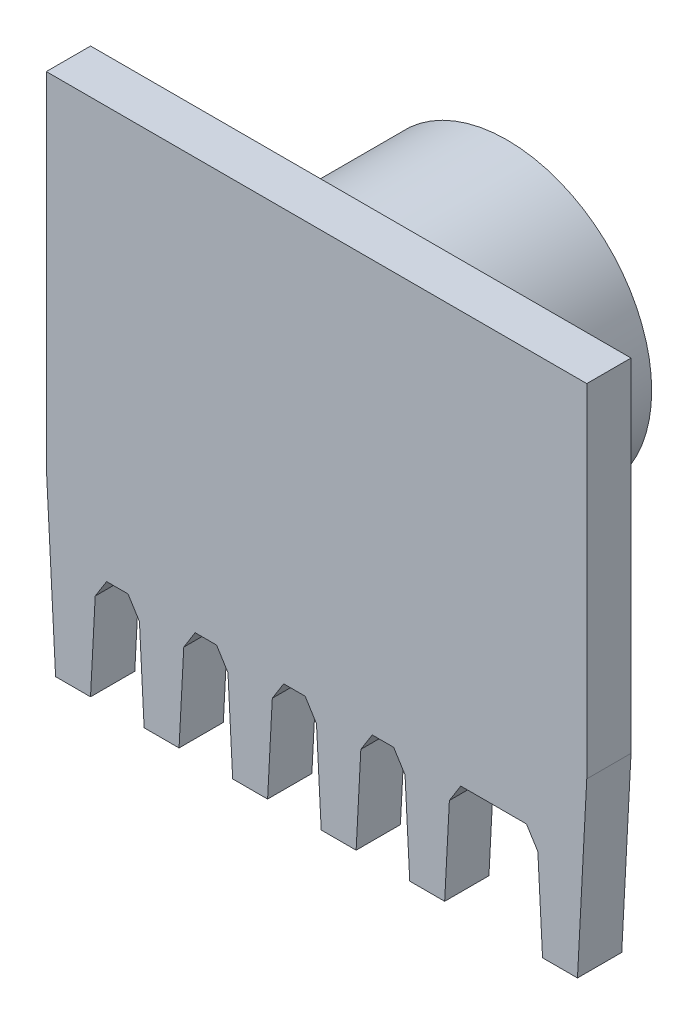
SolidWorks part; units mm, degrees
ref_plane "Front Plane" through (0, 0, 0) normal (0, 0, 1) x (1, 0, 0)
ref_plane "Top Plane" through (0, 0, 0) normal (0, 1, 0) x (1, 0, 0)
ref_plane "Right Plane" through (0, 0, 0) normal (1, 0, 0) x (0, 0, -1)
sketch "Sketch1" plane through (0, 0, 0) normal (0, 0, 1) x (1, 0, 0)
  line L0 (0, 0) -> (0, 17.6) construction
  line L1 (0, 17.6) -> (18.3124, 17.6) construction
  line L2 (18.3124, 17.6) -> (18.3124, 0) construction
  line L3 (18.3124, 0) -> (0, 0) construction
  line L4 (0, 3) -> (18.3124, 3) construction
  line L5 (0, 6) -> (18.3124, 6) construction
  line L6 (0.9062, 6) -> (0.9062, 0) construction
  line L7 (3.9062, 6) -> (3.9062, 0) construction
  line L8 (6.9062, 6) -> (6.9062, 0) construction
  line L9 (9.9062, 6) -> (9.9062, 0) construction
  line L10 (12.9062, 6) -> (12.9062, 0) construction
  line L11 (17.4062, 6) -> (17.4062, 0) construction
  line L12 (0.9062, 3) -> (3.9062, 3) construction
  line L13 (3.9062, 3) -> (6.9062, 3) construction
  line L14 (6.9062, 3) -> (9.9062, 3) construction
  line L15 (9.9062, 3) -> (12.9062, 3) construction
  line L16 (12.9062, 3) -> (17.4062, 3) construction
  line L17 (0.9062, 3) -> (0, 3) construction
  line L18 (17.4062, 3) -> (18.3124, 3) construction
  line L19 (2.4062, 3) -> (2.4062, 0) construction
  line L20 (5.4062, 3) -> (5.4062, 0) construction
  line L21 (8.4062, 3) -> (8.4062, 0) construction
  line L22 (11.4062, 3) -> (11.4062, 0) construction
  line L23 (15.1562, 3) -> (15.1562, 0) construction
  line L24 (14.4062, 3.75) -> (15.9062, 3.75) construction
  line L25 (0, 6) -> (0.3144, 0)
  line L26 (0.3144, 0) -> (1.4979, 0)
  line L27 (1.4979, 0) -> (1.6572, 3.0393)
  line L28 (3.1552, 3.0393) -> (3.3144, 0)
  line L29 (3.3144, 0) -> (4.4979, 0)
  line L30 (4.4979, 0) -> (4.6572, 3.0393)
  line L31 (6.1552, 3.0393) -> (6.3144, 0)
  line L32 (6.3144, 0) -> (7.4979, 0)
  line L33 (7.4979, 0) -> (7.6572, 3.0393)
  line L34 (9.1552, 3.0393) -> (9.3144, 0)
  line L35 (9.3144, 0) -> (10.4979, 0)
  line L36 (10.4979, 0) -> (10.6572, 3.0393)
  line L37 (12.1552, 3.0393) -> (12.3144, 0)
  line L38 (12.3144, 0) -> (13.4979, 0)
  line L39 (13.4979, 0) -> (13.6572, 3.0393)
  line L40 (16.6552, 3.0393) -> (16.8144, 0)
  line L41 (16.8144, 0) -> (17.9979, 0)
  line L42 (17.9979, 0) -> (18.3124, 6)
  line L44 (1.6572, 3.0393) -> (2.0426, 3.656)
  line L45 (0, 6) -> (0, 17.6)
  line L46 (0, 17.6) -> (18.3124, 17.6)
  line L47 (18.3124, 17.6) -> (18.3124, 6)
  line L48 (9.1562, 17.6) -> (9.1562, 6) construction
  line L49 (2.0426, 3.656) -> (2.7698, 3.656)
  line L50 (2.7698, 3.656) -> (3.1552, 3.0393)
  line L51 (4.6572, 3.0393) -> (5.0426, 3.656)
  line L52 (5.0426, 3.656) -> (5.7698, 3.656)
  line L53 (5.7698, 3.656) -> (6.1552, 3.0393)
  line L54 (7.6572, 3.0393) -> (8.0426, 3.656)
  line L55 (8.0426, 3.656) -> (8.7698, 3.656)
  line L56 (8.7698, 3.656) -> (9.1552, 3.0393)
  line L57 (10.6572, 3.0393) -> (11.0426, 3.656)
  line L58 (11.0426, 3.656) -> (11.7698, 3.656)
  line L59 (11.7698, 3.656) -> (12.1552, 3.0393)
  line L60 (13.6572, 3.0393) -> (14.0426, 3.656)
  line L61 (14.0426, 3.656) -> (16.2698, 3.656)
  line L62 (16.2698, 3.656) -> (16.6552, 3.0393)
  line L63 (18.3124, 17.6) -> (18.3124, 18.1) construction
  line L64 (18.3124, 18.1) -> (0, 18.1) construction
  line L65 (0, 18.1) -> (0, 17.6) construction
  arc A0 (3.1552, 3.0393) -> (1.6572, 3.0393) centre (2.4062, 3) ccw construction
  arc A1 (6.1552, 3.0393) -> (4.6572, 3.0393) centre (5.4062, 3) ccw construction
  arc A2 (9.1552, 3.0393) -> (7.6572, 3.0393) centre (8.4062, 3) ccw construction
  arc A3 (12.1552, 3.0393) -> (10.6572, 3.0393) centre (11.4062, 3) ccw construction
  arc A4 (13.6572, 3.0393) -> (14.4062, 3.75) centre (14.4062, 3) cw construction
  arc A5 (16.6552, 3.0393) -> (15.9062, 3.75) centre (15.9062, 3) ccw construction
  dimension "D7" = 0.75
  dimension "D1" = 3
  dimension "D2" = 6
  dimension "D3" = 11.6
  dimension "D4" = 3
  dimension "D5" = 0.5
  dimension "D6" = 4.5
  dimension "D8" = 3
  dimension "D9" = 18.3124
  dimension "D10" = 17.6
extrude "Boss-Extrude1" add sketch "Sketch1" along normal blind 1.5
sketch "Sketch3" plane through (0, 0, 0) normal (0, 0, 1) x (1, 0, 0)
  line L0 (-0.4005, 6) -> (18.7129, 6)
  line L1 (18.7129, 3) -> (-0.4005, 3) construction
  line L2 (-0.4005, 0) -> (18.7129, 0) construction
  line L3 (-0.4005, -0.5) -> (18.7129, -0.5) construction
  line L4 (18.7129, -0.5) -> (18.7129, 6) construction
  line L5 (-0.4005, 6) -> (-0.4005, -0.5) construction
  line L6 (18.3124, 0) -> (0, 0) construction
  line L7 (0, 3) -> (18.3124, 3) construction
  line L8 (0, 6) -> (18.3124, 6) construction
  line L9 (0.3407, -0.5) -> (0, 6) construction
  line L10 (18.3124, 6) -> (17.9717, -0.5) construction
  line L11 (17.9979, 0) -> (18.3124, 6) construction
  line L12 (0, 6) -> (0.3144, 0) construction
  line L13 (5.4062, 6) -> (5.4062, -0.5) construction
  line L14 (3.9062, 6) -> (3.9062, -0.5) construction
  line L15 (5.4062, 3) -> (5.4062, 0) construction
  line L16 (3.1572, 3) -> (3.3407, -0.5) construction
  line L17 (2.7567, 3) -> (2.9401, -0.5)
  line L18 (3.1552, 3.0393) -> (3.3144, 0) construction
  line L19 (2.9401, -0.5) -> (4.8723, -0.5)
  line L20 (4.8723, -0.5) -> (5.0557, 3)
  line L21 (2.8484, 1.25) -> (3.2478, 1.2709) construction
  line L22 (5.9401, -0.5) -> (5.7567, 3)
  line L26 (7.8723, -0.5) -> (5.9401, -0.5)
  line L27 (8.0557, 3) -> (7.8723, -0.5)
  line L30 (2.4062, -0.5) -> (2.4062, 6) construction
  line L31 (2.4062, 3) -> (2.4062, 0) construction
  line L32 (8.4062, 6) -> (8.4062, -0.5) construction
  line L34 (11.4062, -0.5) -> (11.4062, 6) construction
  line L35 (15.1562, -0.5) -> (15.1562, 6) construction
  line L36 (8.4062, 3) -> (8.4062, 0) construction
  line L37 (11.4062, 3) -> (11.4062, 0) construction
  line L38 (15.1562, 3) -> (15.1562, 0) construction
  line L39 (10.8723, -0.5) -> (11.0557, 3)
  line L40 (8.9401, -0.5) -> (10.8723, -0.5)
  line L41 (8.7567, 3) -> (8.9401, -0.5)
  line L42 (11.9401, -0.5) -> (11.7567, 3)
  line L43 (13.8723, -0.5) -> (11.9401, -0.5)
  line L44 (14.0557, 3) -> (13.8723, -0.5)
  line L45 (16.4401, -0.5) -> (18.3723, -0.5)
  line L46 (16.2567, 3) -> (16.4401, -0.5)
  line L47 (18.3723, -0.5) -> (18.7129, 6)
  line L48 (1.8723, -0.5) -> (-0.0599, -0.5)
  line L49 (2.0557, 3) -> (1.8723, -0.5)
  line L50 (-0.0599, -0.5) -> (-0.4005, 6)
  line L51 (16.2567, 3) -> (14.0557, 3)
  line L52 (11.7567, 3) -> (11.0557, 3)
  line L53 (8.7567, 3) -> (8.0557, 3)
  line L54 (5.7567, 3) -> (5.0557, 3)
  line L55 (2.7567, 3) -> (2.0557, 3)
  dimension "D1" = 0.5
  dimension "D2" = 0.4
ref_plane "Plane1" through (3.9062, 0, 0) normal (1, 0, 0) x (0, 0, -1)
sketch "Sketch4" plane through (3.9062, 0, 0) normal (1, 0, 0) x (0, 0, -1)
  line L0 (0, 6) -> (0, -0.5) construction
  line L1 (0.6, 6) -> (-2.1, 6) construction
  line L2 (0.6, 6) -> (0.6, -0.5) construction
  line L3 (0.6, -0.5) -> (-2.1, -0.5) construction
  line L4 (-2.1, 6) -> (-2.1, -0.5) construction
  line L5 (-0.75, -0.5) -> (-0.75, 6) construction
  line L6 (-1.5, 6) -> (-1.5, -0.5) construction
  line L7 (0.6, 2.4005) -> (-2.1, 2.4005) construction
  line L8 (0.3, 6) -> (0.3, -0.5) construction
  line L9 (0.6, 2.4005) -> (3.846, 6) construction
  line L10 (2.2302, 6) -> (0.6, 4.1923) construction
  line L11 (0.6, 4.1923) -> (1.7139, 3.1878) construction
  line L12 (1.7139, 3.1878) -> (4.25, 6)
  line L13 (4.25, 6) -> (0.6, 6) construction
  line L14 (0.3, 1) -> (-1.8, 1) construction
  line L15 (-2.1, 0) -> (0.6, 0) construction
  line L16 (1.7139, 3.1878) -> (1.4912, 3.3887)
  line L17 (1.4912, 3.3887) -> (0.6, 2.4005)
  line L18 (-3.2139, 3.1878) -> (-5.75, 6)
  line L19 (-3.2139, 3.1878) -> (-2.9912, 3.3887)
  line L20 (-2.9912, 3.3887) -> (-2.1, 2.4005)
  line L21 (-2.1, 6) -> (-5.75, 6) construction
  line L22 (0.6, 3.0724) -> (3.2401, 6) construction
  arc A0 (0.4965, 2.2224) -> (0.6, -0.5) centre (4.2, 1) ccw
  arc A1 (0.6, 2.4005) -> (0.4965, 2.2224) centre (0.9713, 2.0656) ccw
  arc A2 (-2.1, 2.4005) -> (-1.9965, 2.2224) centre (-2.4713, 2.0656) cw
  arc A3 (-1.9965, 2.2224) -> (-2.1, -0.5) centre (-5.7, 1) cw
  dimension "D6" = 0.5
  dimension "D1" = 0.6
  dimension "D2" = 0.3
  dimension "D3" = 1.5
  dimension "D4" = 1
  dimension "D5" = 0.3
  dimension "D7" = 10
sketch "Sketch5" plane through (0, 0, 0) normal (1, 0, 0) x (0, 0, -1)
  line L0 (2.2302, 6) -> (0.6, 4.1923) construction
  line L1 (0.6, 4.1923) -> (1.7139, 3.1878) construction
  line L2 (1.7139, 3.1878) -> (4.25, 6) construction
  line L3 (2.2302, 6) -> (0.6, 4.1923) construction
  line L4 (0.6, 4.1923) -> (1.7139, 3.1878) construction
  line L5 (1.7139, 3.1878) -> (4.25, 6) construction
ref_plane "Plane2" through (0, 2.6105, -2.3541) normal (0, 0.7426, -0.6697) x (1, 0, 0)
sketch "Sketch6" plane through (0, 2.6105, -2.3541) normal (0, 0.7426, -0.6697) x (1, 0, 0)
  line L1 (3.9062, -2.362) -> (3.9062, -0.862) construction
  line L2 (3.9062, -2.362) -> (3.9062, -5.0612) construction
  line L3 (4.6562, -5.0612) -> (3.1562, -5.0612)
  line L4 (4.6562, -1.612) -> (3.1562, -1.612) construction
  line L5 (3.1562, -1.612) -> (3.1562, -5.0612)
  line L6 (4.6562, -1.612) -> (4.6562, -5.0612)
  line L10 (2.4062, -5.0612) -> (15.1562, -5.0612) construction
  line L11 (15.1562, -5.0612) -> (15.1562, -0.862) construction
  line L12 (15.1562, -0.862) -> (2.4062, -0.862) construction
  line L13 (2.4062, -0.862) -> (2.4062, -5.0612) construction
  line L14 (15.1562, 0.3349) -> (15.1562, -4.0182) construction
  line L15 (2.4062, 0.3349) -> (2.4062, -4.0182) construction
  line L16 (11.4062, -5.0612) -> (11.4062, -0.862) construction
  line L17 (8.4062, -5.0612) -> (8.4062, -0.862) construction
  line L18 (5.4062, -5.0612) -> (5.4062, -0.862) construction
  line L19 (5.4062, -4.0182) -> (5.4062, 0.3349) construction
  line L20 (8.4062, -4.0182) -> (8.4062, 0.3349) construction
  line L21 (11.4062, 0.3349) -> (11.4062, -4.0182) construction
  line L22 (0.1562, -1.612) -> (0.1562, -5.0612)
  line L23 (0.1562, -5.0612) -> (1.6562, -5.0612)
  line L24 (1.6562, -1.612) -> (1.6562, -5.0612)
  line L25 (7.6562, -1.612) -> (7.6562, -5.0612)
  line L26 (6.1562, -5.0612) -> (7.6562, -5.0612)
  line L27 (6.1562, -1.612) -> (6.1562, -5.0612)
  line L28 (10.6562, -1.612) -> (10.6562, -5.0612)
  line L29 (10.6562, -5.0612) -> (9.1562, -5.0612)
  line L30 (9.1562, -1.612) -> (9.1562, -5.0612)
  line L31 (13.6562, -1.612) -> (13.6562, -5.0612)
  line L32 (12.1562, -5.0612) -> (13.6562, -5.0612)
  line L33 (12.1562, -1.612) -> (12.1562, -5.0612)
  line L34 (18.1562, -1.612) -> (18.1562, -5.0612)
  line L35 (18.1562, -5.0612) -> (16.6562, -5.0612)
  line L36 (16.6562, -1.612) -> (16.6562, -5.0612)
  circle A0 centre (3.9062, -1.612) radius 0.75 construction
  arc A1 (4.6562, -1.612) -> (3.1562, -1.612) centre (3.9062, -1.612) ccw
  arc A2 (0.1562, -1.612) -> (1.6562, -1.612) centre (0.9062, -1.612) cw
  arc A3 (6.1562, -1.612) -> (7.6562, -1.612) centre (6.9062, -1.612) cw
  arc A4 (10.6562, -1.612) -> (9.1562, -1.612) centre (9.9062, -1.612) ccw
  arc A5 (12.1562, -1.612) -> (13.6562, -1.612) centre (12.9062, -1.612) cw
  arc A6 (18.1562, -1.612) -> (16.6562, -1.612) centre (17.4062, -1.612) ccw
ref_plane "Plane3" through (0, 1.6223, -1.463) normal (0, 0.7426, -0.6697) x (1, 0, 0)
sketch "Sketch7" plane through (0, 1.6223, -1.463) normal (0, 0.7426, -0.6697) x (1, 0, 0)
  line L0 (3.1562, -1.612) -> (3.1562, -5.0612) construction
  line L1 (4.6562, -5.0612) -> (3.1562, -5.0612) construction
  line L2 (4.6562, -1.612) -> (4.6562, -5.0612) construction
  line L3 (3.1562, -1.612) -> (3.1562, -5.0612) construction
  line L4 (4.6562, -5.0612) -> (3.1562, -5.0612) construction
  line L5 (4.6562, -1.612) -> (4.6562, -5.0612) construction
  line L6 (3.9062, -0.862) -> (3.9062, -5.0612) construction
  line L7 (4.6562, -1.612) -> (3.1562, -1.612) construction
  line L8 (4.6562, -2.362) -> (3.1562, -2.362) construction
  line L9 (3.4562, -1.612) -> (3.4562, -2.362)
  line L10 (3.4562, -2.362) -> (4.3562, -2.362)
  line L11 (4.3562, -2.362) -> (4.3562, -1.612)
  line L12 (2.4062, -0.862) -> (2.4062, -5.0612) construction
  line L13 (2.4062, -5.0612) -> (15.1562, -5.0612) construction
  line L14 (15.1562, -0.862) -> (2.4062, -0.862) construction
  line L15 (5.4062, -5.0612) -> (5.4062, -0.862) construction
  line L16 (8.4062, -5.0612) -> (8.4062, -0.862) construction
  line L17 (11.4062, -5.0612) -> (11.4062, -0.862) construction
  line L18 (15.1562, -5.0612) -> (15.1562, -0.862) construction
  line L19 (2.4062, -0.862) -> (2.4062, -5.0612) construction
  line L20 (2.4062, -5.0612) -> (15.1562, -5.0612) construction
  line L21 (15.1562, -0.862) -> (2.4062, -0.862) construction
  line L22 (5.4062, -5.0612) -> (5.4062, -0.862) construction
  line L23 (8.4062, -5.0612) -> (8.4062, -0.862) construction
  line L24 (11.4062, -5.0612) -> (11.4062, -0.862) construction
  line L25 (15.1562, -5.0612) -> (15.1562, -0.862) construction
  line L26 (0.4562, -2.362) -> (0.4562, -1.612)
  line L27 (1.3562, -2.362) -> (0.4562, -2.362)
  line L28 (1.3562, -1.612) -> (1.3562, -2.362)
  line L29 (7.3562, -2.362) -> (6.4562, -2.362)
  line L30 (7.3562, -1.612) -> (7.3562, -2.362)
  line L31 (6.4562, -2.362) -> (6.4562, -1.612)
  line L32 (9.4562, -1.612) -> (9.4562, -2.362)
  line L33 (10.3562, -2.362) -> (10.3562, -1.612)
  line L34 (9.4562, -2.362) -> (10.3562, -2.362)
  line L35 (13.3562, -1.612) -> (13.3562, -2.362)
  line L36 (12.4562, -2.362) -> (12.4562, -1.612)
  line L37 (13.3562, -2.362) -> (12.4562, -2.362)
  line L38 (16.9562, -1.612) -> (16.9562, -2.362)
  line L39 (17.8562, -2.362) -> (17.8562, -1.612)
  line L40 (16.9562, -2.362) -> (17.8562, -2.362)
  arc A0 (4.6562, -1.612) -> (3.1562, -1.612) centre (3.9062, -1.612) ccw construction
  arc A1 (4.6562, -1.612) -> (3.1562, -1.612) centre (3.9062, -1.612) ccw construction
  circle A2 centre (3.9062, -1.612) radius 0.45 construction
  arc A3 (4.3562, -1.612) -> (3.4562, -1.612) centre (3.9062, -1.612) ccw
  arc A4 (0.4562, -1.612) -> (1.3562, -1.612) centre (0.9062, -1.612) cw
  arc A5 (6.4562, -1.612) -> (7.3562, -1.612) centre (6.9062, -1.612) cw
  arc A6 (10.3562, -1.612) -> (9.4562, -1.612) centre (9.9062, -1.612) ccw
  arc A7 (12.4562, -1.612) -> (13.3562, -1.612) centre (12.9062, -1.612) cw
  arc A8 (17.8562, -1.612) -> (16.9562, -1.612) centre (17.4062, -1.612) ccw
ref_plane "bisect" through (0, 0, 0.75) normal (0, 0, 1) x (1, 0, 0)
ref_plane "insert_surface" through (0, 6, 0) normal (0, 1, 0) x (1, 0, 0)
sketch "Sketch8" plane through (0, 6, 0) normal (0, 1, 0) x (1, 0, 0)
  line L0 (18.7129, -0.75) -> (-0.4005, -0.75) construction
  line L1 (-0.4005, 0.6) -> (18.7129, 0.6)
  line L2 (-0.4005, 0.6) -> (-0.4005, -2.1)
  line L3 (-0.4005, -2.1) -> (18.7129, -2.1)
  line L4 (18.7129, 0.6) -> (18.7129, -2.1)
  line L5 (9.1562, 0.6) -> (9.1562, -2.1) construction
  line L6 (0, 0) -> (18.3124, 0) construction
  line L7 (0, 0) -> (0, -1.5) construction
  line L8 (0, -1.5) -> (18.3124, -1.5) construction
  line L9 (18.3124, 0) -> (18.3124, -1.5) construction
  line L10 (18.7129, 0.3) -> (-0.4005, 0.3) construction
  line L11 (18.7129, -1.8) -> (-0.4005, -1.8) construction
sketch "Sketch9" plane through (0, 0, 0) normal (0, 0, 1) x (1, 0, 0)
  line L0 (18.3723, -0.5) -> (18.7129, 6) construction
  line L1 (-0.4005, 6) -> (18.7129, 6) construction
  line L2 (-0.0599, -0.5) -> (-0.4005, 6) construction
  line L3 (1.8723, -0.5) -> (-0.0599, -0.5) construction
  line L4 (2.0557, 3) -> (1.8723, -0.5) construction
  line L5 (2.7567, 3) -> (2.0557, 3) construction
  line L6 (2.7567, 3) -> (2.9401, -0.5) construction
  line L7 (2.9401, -0.5) -> (4.8723, -0.5) construction
  line L8 (4.8723, -0.5) -> (5.0557, 3) construction
  line L9 (5.7567, 3) -> (5.0557, 3) construction
  line L10 (5.9401, -0.5) -> (5.7567, 3) construction
  line L11 (7.8723, -0.5) -> (5.9401, -0.5) construction
  line L12 (8.0557, 3) -> (7.8723, -0.5) construction
  line L13 (8.7567, 3) -> (8.0557, 3) construction
  line L14 (8.7567, 3) -> (8.9401, -0.5) construction
  line L15 (8.9401, -0.5) -> (10.8723, -0.5) construction
  line L16 (10.8723, -0.5) -> (11.0557, 3) construction
  line L17 (11.7567, 3) -> (11.0557, 3) construction
  line L18 (11.9401, -0.5) -> (11.7567, 3) construction
  line L19 (13.8723, -0.5) -> (11.9401, -0.5) construction
  line L20 (14.0557, 3) -> (13.8723, -0.5) construction
  line L21 (16.2567, 3) -> (14.0557, 3) construction
  line L22 (16.2567, 3) -> (16.4401, -0.5) construction
  line L23 (16.4401, -0.5) -> (18.3723, -0.5) construction
  line L24 (18.3723, -0.5) -> (18.7129, 6)
  line L25 (-0.4005, 6) -> (18.7129, 6) construction
  line L26 (-0.0599, -0.5) -> (-0.4005, 6)
  line L27 (1.8723, -0.5) -> (-0.0599, -0.5)
  line L28 (2.0557, 3) -> (1.8723, -0.5)
  line L29 (2.7567, 3) -> (2.0557, 3) construction
  line L30 (2.7567, 3) -> (2.9401, -0.5)
  line L31 (2.9401, -0.5) -> (4.8723, -0.5)
  line L32 (4.8723, -0.5) -> (5.0557, 3)
  line L33 (5.7567, 3) -> (5.0557, 3) construction
  line L34 (5.9401, -0.5) -> (5.7567, 3)
  line L35 (7.8723, -0.5) -> (5.9401, -0.5)
  line L36 (8.0557, 3) -> (7.8723, -0.5)
  line L37 (8.7567, 3) -> (8.0557, 3) construction
  line L38 (8.7567, 3) -> (8.9401, -0.5)
  line L39 (8.9401, -0.5) -> (10.8723, -0.5)
  line L40 (10.8723, -0.5) -> (11.0557, 3)
  line L41 (11.7567, 3) -> (11.0557, 3) construction
  line L42 (11.9401, -0.5) -> (11.7567, 3)
  line L43 (13.8723, -0.5) -> (11.9401, -0.5)
  line L44 (14.0557, 3) -> (13.8723, -0.5)
  line L45 (16.2567, 3) -> (14.0557, 3) construction
  line L46 (16.2567, 3) -> (16.4401, -0.5)
  line L47 (16.4401, -0.5) -> (18.3723, -0.5)
  line L48 (16.2567, 3) -> (16.2567, 6)
  line L49 (14.0557, 3) -> (14.0557, 6)
  line L50 (11.7567, 3) -> (11.7567, 6)
  line L51 (18.7129, 6) -> (-0.4005, 6) construction
  line L52 (11.0557, 3) -> (11.0557, 6)
  line L53 (-0.4005, 6) -> (18.7129, 6) construction
  line L54 (8.7567, 3) -> (8.7567, 6)
  line L55 (8.0557, 3) -> (8.0557, 6)
  line L58 (5.7567, 3) -> (5.7567, 6)
  line L60 (5.0557, 3) -> (5.0557, 6)
  line L62 (15.1562, -0.5) -> (15.1562, 6) construction
  line L63 (15.1562, -0.5) -> (15.1562, 6) construction
  line L64 (2.7567, 3) -> (2.7567, 6)
  line L65 (2.0557, 3) -> (2.0557, 6)
  line L67 (18.7129, 6) -> (16.2567, 6)
  line L68 (14.0557, 6) -> (11.7567, 6)
  line L69 (11.0557, 6) -> (8.7567, 6)
  line L70 (8.0557, 6) -> (5.7567, 6)
  line L71 (5.0557, 6) -> (2.7567, 6)
  line L72 (2.0557, 6) -> (-0.4005, 6)
sketch "rgb_led" plane through (0, 0, 1.5) normal (0, 0, 1) x (1, 0, 0)
  line L0 (18.3124, 14.6) -> (0, 14.6) construction
  line L1 (18.3124, 6) -> (18.3124, 17.6) construction
  line L2 (0, 17.6) -> (0, 6) construction
  line L3 (9.1562, 17.6) -> (9.1562, 14.6) construction
  line L4 (18.3124, 17.6) -> (0, 17.6) construction
  line L6 (12.0562, 16.4) -> (6.2562, 16.4)
  line L7 (12.0562, 16.4) -> (12.0562, 12.8)
  line L8 (12.0562, 12.8) -> (6.2562, 12.8)
  line L9 (6.2562, 16.4) -> (6.2562, 12.8)
  dimension "D1" = 3
  dimension "D2" = 3.6
  dimension "D3" = 5.8
sketch "Sketch10" plane through (0, 0, 0) normal (0, 0, 1) x (1, 0, 0)
  line L0 (0, 6) -> (18.3124, 6) construction
  line L1 (0, 6) -> (0, 17.6) construction
  line L2 (0, 17.6) -> (18.3124, 17.6) construction
  line L3 (9.1124, 12) -> (9.1124, 6) construction
  line L4 (9.1124, 12) -> (18.3124, 12) construction
  line L5 (18.3124, 6) -> (18.3124, 17.6) construction
  circle A0 centre (9.1124, 12) radius 4.9
  dimension "D3" = 9.8
  dimension "D1" = 9.2
  dimension "D2" = 6
extrude "Boss-Extrude2" add sketch "Sketch10" against normal blind 5
ref_plane "right_center" through (9.1562, 0, 0) normal (1, 0, 0) x (0, 0, -1)
sketch "Sketch11" plane through (0, 6, 0) normal (0, 1, 0) x (1, 0, 0)
  line L0 (18.7112, -0.75) -> (9.1562, -0.75) construction
  line L1 (18.7112, -2.1) -> (-0.3988, -2.1)
  line L2 (18.7112, -2.1) -> (18.7112, 0.6)
  line L3 (18.7112, 0.6) -> (-0.3988, 0.6)
  line L4 (-0.3988, -2.1) -> (-0.3988, 0.6)
  line L5 (9.1562, -0.75) -> (9.1562, -2.1) construction
  line L6 (9.1562, -0.75) -> (-0.3988, -0.75) construction
  line L7 (9.1562, 0.6) -> (9.1562, -0.75) construction
  dimension "D1" = 2.7
  dimension "D2" = 19.11
ref_plane "clear_plane" through (0, 18.1, 0) normal (0, 1, 0) x (1, 0, 0)
sketch "Sketch12" plane through (0, 18.1, 0) normal (0, 1, 0) x (1, 0, 0)
  line L0 (-0.5, -2) -> (18.8124, -2)
  line L1 (18.8124, -2) -> (18.8124, 0.5)
  line L2 (18.8124, 0.5) -> (-0.5, 0.5)
  line L3 (-0.5, 0.5) -> (-0.5, -2)
  line L4 (18.3124, 0) -> (0, 0)
  line L5 (0, 0) -> (0, -1.5)
  line L6 (0, -1.5) -> (18.3124, -1.5)
  line L7 (18.3124, -1.5) -> (18.3124, 0)
  line L8 (18.3124, 0) -> (0, 0) construction
  line L9 (0, 0) -> (0, -1.5) construction
  line L10 (0, -1.5) -> (18.3124, -1.5) construction
  line L11 (18.3124, -1.5) -> (18.3124, 0) construction
  dimension "D1" = 0
  dimension "D2" = 0.5
